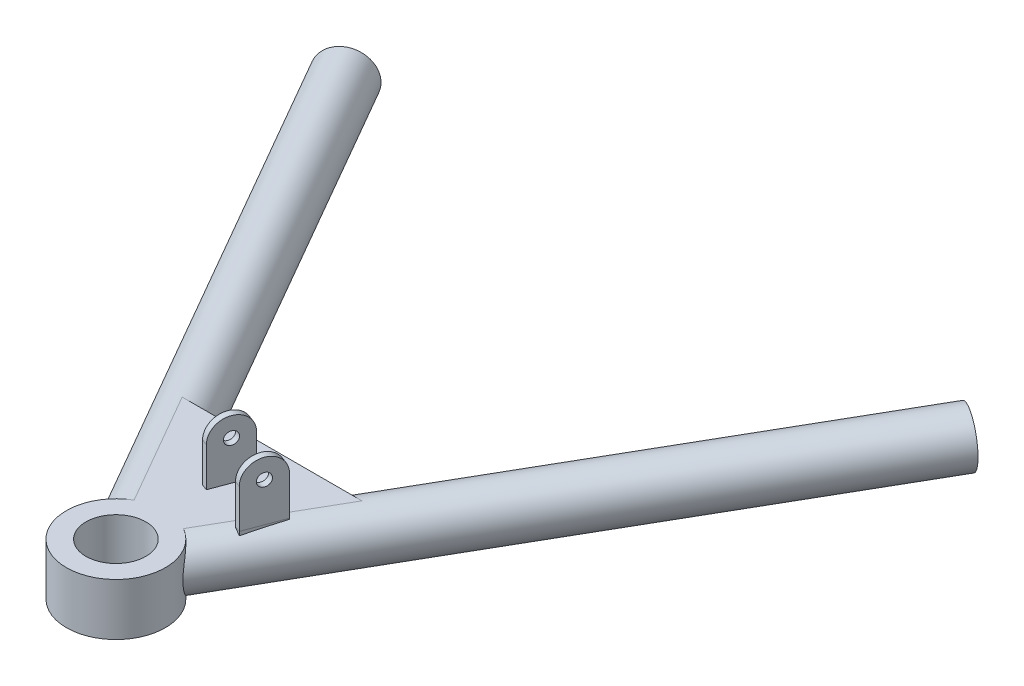
SolidWorks part; units mm, degrees
note: The reader was unsure of these and kept them because the rebuilt part matched: shared geometry of "Sketch14<3>".
material "AISI 4130 Steel, annealed at 865C"
ref_plane "Front Plane" through (0, 0, 0) normal (0, 0, 1) x (1, 0, 0)
ref_plane "Top Plane" through (0, 0, 0) normal (0, 1, 0) x (1, 0, 0)
ref_plane "Right Plane" through (0, 0, 0) normal (1, 0, 0) x (0, 0, -1)
sketch "Sketch1" plane through (0, 0, 0) normal (0, 1, 0) x (1, 0, 0)
  circle A0 centre (0, 0) radius 11.5062
  circle A1 centre (0, 0) radius 19.0062
  dimension "D3" = 23.0124
  dimension "D1" = 38.0124
extrude "Boss-Extrude1" add sketch "Sketch1" along normal mid plane 20
sketch "Sketch3" plane through (0, 0, 0) normal (0, 1, 0) x (1, 0, 0)
  line L0 (-19.0062, 0) -> (19.0062, 0) construction
  line L1 (0, 0) -> (-135.5, 235.3859) construction
  line L2 (0, 0) -> (119.6742, 207.8939) construction
  line L3 (-9.4821, 16.472) -> (-135.5, 235.3859) construction
  line L4 (9.4821, 16.472) -> (119.6742, 207.8939) construction
  line L6 (119.6742, 207.8939) -> (142.2716, 194.8857) construction
  line L7 (-119.6742, 207.8939) -> (-147.9725, 191.604) construction
  line L8 (0, 0) -> (135.5, 235.3859) construction
  line L9 (135.5, 235.3859) -> (-135.5, 235.3859) construction
  circle A0 centre (0, 0) radius 19.0062 construction
  circle A1 centre (0, 0) radius 19.0062 construction
  dimension "D1" = 60.073
  dimension "D2" = 60.073
  dimension "D3" = 271.6004
  dimension "D5" = 31.7217
  dimension "D4" = 271.6004
  dimension "D6" = 31.7217
ref_plane "tube1plane" through (119.6742, 0, -207.8939) normal (0.4989, 0, -0.8667) x (0.8667, 0, 0.4989)
ref_plane "tube2plane" through (-119.6742, 0, -207.8939) normal (-0.4989, 0, -0.8667) x (-0.8667, 0, 0.4989)
sketch "Sketch5" plane through (119.6742, 0, -207.8939) normal (0.4989, 0, -0.8667) x (0.8667, 0, 0.4989)
  circle A0 centre (0, 0) radius 10
  circle A1 centre (0, 0) radius 7
  dimension "D1" = 20
  dimension "D2" = 14
extrude "Boss-Extrude2" add sketch "Sketch5" against normal up to next
sketch "Sketch6" plane through (-119.6742, 0, -207.8939) normal (-0.4989, 0, -0.8667) x (-0.8667, 0, 0.4989)
  circle A0 centre (0, 0) radius 10
  circle A1 centre (0, 0) radius 7
  dimension "D1" = 20
  dimension "D2" = 14
extrude "Boss-Extrude3" add sketch "Sketch6" against normal up to surface (223.7159 mm away)
sketch "Sketch13" plane through (0, 10, 0) normal (0, 1, 0) x (1, 0, 0)
  line L0 (9.4821, 16.472) -> (34.539, 60)
  line L1 (-9.4821, 16.472) -> (-34.539, 60)
  line L2 (0, 0) -> (-135.5, 235.3859) construction
  line L3 (0, 0) -> (119.6742, 207.8939) construction
  line L4 (34.539, 60) -> (-34.539, 60)
  arc A1 (9.4821, 16.472) -> (0, 19.0062) centre (0, 0) ccw construction
  arc A2 (9.4821, 16.472) -> (-9.4821, 16.472) centre (0, 0) ccw construction
  arc A3 (9.4821, 16.472) -> (-9.4821, 16.472) centre (0, 0) ccw
  dimension "D1" = 60
extrude "Boss-Extrude7" add sketch "Sketch13" against normal blind 7.5
sketch3d "3DSketch1"
  line L0 (0, 0, 0) -> (0, 0, -37.5) construction
  line L1 (0, 0, -37.5) -> (12.5, 0, -37.5) construction
  line L2 (12.5, 0, -37.5) -> (12.5, 25, -37.5) construction
  line L3 (12.5, 0, -37.5) -> (-1.4912, 0, 0) construction
  line L4 (-1.4912, 0, 0) -> (-1.4912, 0, -32.7272) construction
  line L5 (-19.0062, 0, 0) -> (19.0062, 0, 0) construction
  dimension "D1" = 37.5
  dimension "D2" = 12.5
  dimension "D3" = 25
  dimension "D4" = 20.46
ref_plane "Plane1" through (-1.309, 0, -0.4884) normal (-0.9369, 0, -0.3496) x (-0.3496, 0, 0.9369)
sketch "Sketch14" plane through (-1.309, 0, -0.4884) normal (-0.9369, 0, -0.3496) x (-0.3496, 0, 0.9369)
  line L0 (-47.0038, 10) -> (-47.0038, 25)
  line L1 (-39.5038, 8.6439) -> (-39.5038, 32.5) construction
  line L2 (-39.5038, 0) -> (-39.5038, 25) construction
  line L3 (-32.0038, 10) -> (-32.0038, 25)
  line L4 (-47.0038, 10) -> (-32.0038, 10)
  line L5 (19.0062, 10) -> (-18.7474, 10) construction
  circle A0 centre (-39.5038, 25) radius 2.413
  arc A1 (-32.0038, 25) -> (-47.0038, 25) centre (-39.5038, 25) ccw
  dimension "D1" = 4.826
  dimension "D2" = 7.5
extrude "Boss-Extrude8" add sketch "Sketch14" along normal mid plane 24.05
extrude "Cut-Extrude1" cut sketch "Sketch14<3>" against normal mid plane 19.05
sketch "Sketch14<3>" plane through (-1.309, 0, -0.4884) normal (-0.9369, 0, -0.3496) x (-0.3496, 0, 0.9369) same geometry as "Sketch14"
sketch "Sketch15" plane through (9.9574, 0, 3.7151) normal (0.9369, 0, 0.3496) x (0.3496, 0, -0.9369)
  line L0 (39.5038, 0) -> (39.5038, 25) construction
  line L1 (47.0038, 8) -> (32.0038, 8)
  line L2 (47.0038, 8) -> (47.0038, 10)
  line L3 (47.0038, 10) -> (32.0038, 10)
  line L4 (32.0038, 8) -> (32.0038, 10)
  line L5 (47.0038, 8) -> (32.0038, 10) construction
  line L6 (47.0038, 10) -> (32.0038, 8) construction
  point P0 (39.5038, 9)
  dimension "D1" = 2
extrude "Boss-Extrude9" add sketch "Sketch15" against normal up to surface (2.5 mm away)
equation "\"CA_ID\"= 14"
equation "\"D2@Sketch5\"=\"CA_ID\""
equation "\"D2@Sketch6\"=\"CA_ID\""
equation "\"tube_end_to_ball_center\" = 31.721675mm"
equation "\"D6@Sketch3\"=\"tube_end_to_ball_center\""
equation "\"D5@Sketch3\"=\"tube_end_to_ball_center\""
